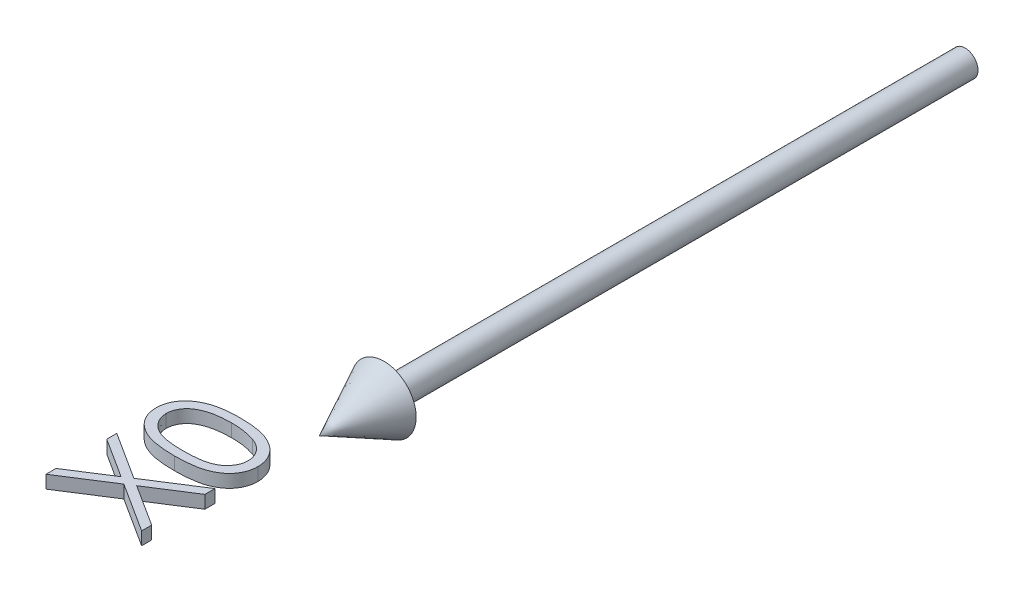
SolidWorks part; units mm, degrees
ref_plane "Front Plane" through (0, 0, 0) normal (0, 0, 1) x (1, 0, 0)
ref_plane "Top Plane" through (0, 0, 0) normal (0, 1, 0) x (1, 0, 0)
ref_plane "Right Plane" through (0, 0, 0) normal (1, 0, 0) x (0, 0, -1)
sketch "Sketch2" plane through (0, 0, 0) normal (0, 1, 0) x (1, 0, 0)
  line L0 (0, 41.95) -> (0, -114.4521) construction
  line L1 (-36.8894, 0) -> (41.4965, 0) construction
  line L2 (0, -100) -> (5, -90)
  line L3 (5, -90) -> (2, -90)
  line L4 (2, -90) -> (2, 0)
  line L5 (2, 0) -> (0, 0)
  line L6 (0, 0) -> (0, -100)
  dimension "D1" = 100
  dimension "D2" = 2
  dimension "D3" = 10
  dimension "D4" = 5
revolve "Revolve1" add sketch "Sketch2" angle 360 about L0
sketch "Sketch3" plane through (0, 0, 0) normal (0, 1, 0) x (1, 0, 0)
  line L0 (0, -103.9528) -> (0, -147.2622) construction
  line L1 (-18.6107, -118.3811) -> (18.3141, -118.3811) construction
  text T0 "X0" font "Century Gothic" height 15
extrude "Boss-Extrude1" add sketch "Sketch3" against normal blind 1 and the other way blind 1 separate body
equation "\"frame_arrow_length\"=100"
equation "\"D1@Sketch2\"=\"frame_arrow_length\""
equation "\"frame_arrow_odA\"=4"
equation "\"D2@Sketch2\"=\"frame_arrow_odA\"/2"
equation "\"frame_arrow_head_od\"=5"
equation "\"D4@Sketch2\"=\"frame_arrow_head_od\""
equation "\"frame_arrow_head_length\"=10"
equation "\"D3@Sketch2\"=\"frame_arrow_head_length\""
equation "\"tvarobot_theta1\"=30"
equation "\"link0_ringA_odA\"= 40"
equation "\"link0_ringA_odB\"= 25"
equation "\"link0_ringA_id\"= 20"
equation "\"link0_ringA_thickness\"= (\"link0_ringA_odB\" - \"link0_ringA_id\")/2"
equation "\"link0_ringA_height\"= 3"
equation "\"link0_ringA_heightA\"= 1.5"
equation "\"link0_ringA_heightB\"=\"link0_ringA_height\"-\"link0_ringA_heightA\""
equation "\"link0_ringB_odA\"= 40"
equation "\"link0_ringB_odB\"= 29"
equation "\"link0_ringB_id\"= \"link0_shaftA_bearing_id\"+1"
equation "\"link0_ringB_thickness\"= (\"link0_ringB_odB\" - \"link0_ringB_id\")/2"
equation "\"link0_ringB_height\"= 3"
equation "\"link0_ringB_heightA\"= 1.5"
equation "\"link0_ringB_heightB\"=\"link0_ringB_height\"-\"link0_ringB_heightA\""
equation "\"link0_shaftA_bearing_od\"=27"
equation "\"link0_shaftA_bearing_id\"=20"
equation "\"link0_shaftA_thrust_bearing_od\"=35"
equation "\"link0_shaftA_thrust_bearing_id\"=20.04"
equation "\"link0_shaftA_retaining_ring_id\"=18.5"
equation "\"link0_shaftA_retaining_ring_groove_width\"=1.5"
equation "\"link0_shaftA_spline_length\"=8.0"
equation "\"link0_shaftA_spline_depth\"=1.0"
equation "\"link0_shaftA_spline_width\"=4.0"
equation "\"link0_shaftA_odA\"=\"link0_shaftA_bearing_id\""
equation "\"link0_shaftA_odB\"=35"
equation "\"link0_shaftA_odC\"=\"link0_shaftA_bearing_id\""
equation "\"link0_shaftA_odD\"=\"link0_shaftA_odC\"-2*\"link0_shaftA_spline_depth\""
equation "\"link0_shaftA_odE\"=\"link0_shaftA_bearing_id\""
equation "\"link0_shaftA_odF\"=\"link0_shaftA_odE\"-2*\"link0_shaftA_spline_depth\""
equation "\"link0_shaftA_idA\"=10"
equation "\"link0_shaftA_idB\"=6"
equation "\"link0_shaftA_length\"=39.5"
equation "\"link0_shaftA_lengthA\"=8.0"
equation "\"link0_shaftA_lengthB\"=12.0"
equation "\"link0_shaftA_lengthC\"=35.0"
equation "\"link0_shaftA_lengthD\"=39.0"
equation "\"link0_shaftA_lengthE\"=\"link0_shaftA_length\"-\"link0_shaftA_lengthD\""
equation "\"link0_shaftA_offsetX\"=11"
equation "\"link0_shaftA_offsetY\"=0"
equation "\"link0_shaftA_bolt_pattern_dia\"=14"
equation "\"link0_motor_center_dist\"=26"
equation "\"link0_46t_pulley_spline_length\"=8"
equation "\"link0_46t_pulley_spline_depth\"=\"link0_shaftA_spline_depth\"*1.025"
equation "\"link0_46t_pulley_spline_width\"=\"link0_shaftA_spline_width\"*1.05"
equation "\"link0_46t_pulley_idA\"=\"link0_shaftA_bearing_id\"*1.025"
equation "\"link0_46t_pulley_idB\"=\"link0_46t_pulley_idA\"-2*\"link0_46t_pulley_spline_depth\""
equation "\"link0_shaftB_spline_length\"=10"
equation "\"link0_shaftB_spline_depth\"=1.0"
equation "\"link0_shaftB_spline_width\"=1.25"
equation "\"link0_shaftB_length\"=7"
equation "\"link0_shaftB_lengthA\"=1.5"
equation "\"link0_shaftB_lengthB\"=2.75"
equation "\"link0_shaftB_odA\"=32"
equation "\"link0_shaftB_odB\"=22"
equation "\"link0_shaftB_odC\"=20"
equation "\"link0_shaftB_idA\"=10"
equation "\"link0_shaftB_bolt_diameter\"=19"
equation "\"link0_shaftB_bearing_od\"=27"
equation "\"link0_shaftB_bearing_id\"=20"
equation "\"link0_motor_length\"=46.5"
equation "\"link0_motor_width\"=28.5"
equation "\"link0_motor_height\"=34"
equation "\"link0_motor_offset\"=8"
equation "\"link0_shellA_thickness\"=2.5"
equation "\"link0_shellB_thickness\"=\"link0_shellA_thickness\""
equation "\"link0_plateA_shellA_height\"=48"
equation "\"link0_shellA_width\" =\"link0_plateA_width\""
equation "\"link0_shellA_height\" = \"link0_plateA_shellA_height\"-\"link0_plateA_height\""
equation "\"link0_shellA_length\" = \"link0_plateA_lengthB\" "
equation "\"link0_shellB_length\"=\"link0_shellA_length\""
equation "\"link0_shellA_radius\" = 0.375*25.4"
equation "\"link0_shellA_radiusA\"= \"link0_plateA_radiusA\""
equation "\"link0_shellA_radiusB\"= \"link0_plateA_radiusB\""
equation "\"link0_shellA_radiusC\"= 3"
equation "\"link0_postA_height\"=7"
equation "\"link0_postA_width\"=16"
equation "\"link0_postA_length\"=20"
equation "\"link0_postA_posX\"=22"
equation "\"link0_postA_posY\"=17.5"
equation "\"link0_postA_pocket_width\"=6.0"
equation "\"link0_postA_pocket_length\"=2.5"
equation "\"link0_postA_pocket_depth\"=9"
equation "\"link0_postA_pocket_posZ\"=10"
equation "\"link0_postB_height\"=7"
equation "\"link0_postB_width\"=16"
equation "\"link0_postB_length\"=20"
equation "\"link0_postB_posX\"=22"
equation "\"link0_postB_posY\"=17.5"
equation "\"link0_postB_id\"=3.0"
equation "\"link0_postB_pocket_width\"=6.0"
equation "\"link0_postB_pocket_length\"=2.5"
equation "\"link0_postB_pocket_depth\"=9"
equation "\"link0_postB_pocket_posZ\"=10"
equation "\"link0_postC_height\"=7"
equation "\"link0_postC_width\"=16"
equation "\"link0_postC_length\"=20"
equation "\"link0_postC_posX\"=22"
equation "\"link0_postC_posY\"=17.5"
equation "\"link0_postC_id\"=3.0"
equation "\"link0_postC_pocket_width\"=6.0"
equation "\"link0_postC_pocket_length\"=2.5"
equation "\"link0_postC_pocket_depth\"=9"
equation "\"link0_postC_pocket_posZ\"=10"
equation "\"link0_postD_height\"=7"
equation "\"link0_postD_width\"=16"
equation "\"link0_postD_length\"=20"
equation "\"link0_postD_posX\"=22"
equation "\"link0_postD_posY\"=17.5"
equation "\"link0_postD_id\"=3.0"
equation "\"link0_postD_pocket_width\"=6.0"
equation "\"link0_postD_pocket_length\"=3.0"
equation "\"link0_postD_pocket_depth\"=9"
equation "\"link0_postD_pocket_posZ\"=10"
equation "\"link0_postE_height\"=5"
equation "\"link0_postE_width\"=16"
equation "\"link0_postE_length\"=\"link0_plateE_lengthA\"-\"link0_lip_height\""
equation "\"link0_postE_posZ\"=22"
equation "\"link0_postE_posX\"=17.5"
equation "\"link0_postE_posY\"=22"
equation "\"link0_postE_id\"=3.0"
equation "\"link0_postE_cbore_id\"=6.5"
equation "\"link0_postE_hole_id\"=3"
equation "\"link0_postF_posZ\"=22"
equation "\"link0_postF_posX\"=17.5"
equation "\"link0_postF_posY\"=\"link0_plateB_lengthA\"+4"
equation "\"link0_postF_id\"=3.0"
equation "\"link0_postF_cbore_id\"=6.5"
equation "\"link0_postF_hole_id\"=3"
equation "\"link0_postG_posZ\"=22"
equation "\"link0_postG_posX\"=17.5"
equation "\"link0_postG_posY\"=\"link0_plateB_lengthA\"+12"
equation "\"link0_postG_id\"=3.0"
equation "\"link0_postG_cbore_id\"=6.5"
equation "\"link0_postG_hole_id\"=3"
equation "\"link0_postHIJ_posY\"=6"
equation "\"link0_postH_posX\"=28"
equation "\"link0_postH_posY\"=20"
equation "\"link0_postH_posZ\"=20"
equation "\"link0_postH_length\"=10"
equation "\"link0_postI_posX\"=28"
equation "\"link0_postI_posY\"=20"
equation "\"link0_postI_posZ\"=135"
equation "\"link0_postI_length\"=10"
equation "\"link0_postJ_posX\"=28"
equation "\"link0_postJ_posY\"=20"
equation "\"link0_postJ_posZ\"=175"
equation "\"link0_postJ_length\"=10"
equation "\"link0_postK_posX\"=28"
equation "\"link0_postK_posY\"=20"
equation "\"link0_postK_posZ\"=175"
equation "\"link0_postK_length\"=10"
equation "\"link0_postL_posX\"=28"
equation "\"link0_postL_posY\"=20"
equation "\"link0_postL_posZ\"=135"
equation "\"link0_postL_length\"=10"
equation "\"link0_postM_posX\"=28"
equation "\"link0_postM_posY\"=20"
equation "\"link0_postM_posZ\"=35"
equation "\"link0_postM_length\"=10"
equation "\"link0_plateA_lengthA\"=30"
equation "\"link0_plateA_lengthB\"=150"
equation "\"link0_plateA_lengthC\"=30"
equation "\"link0_plateA_length\"=\"link0_plateA_lengthA\"+\"link0_plateA_lengthB\"+\"link0_plateA_lengthC\""
equation "\"link0_plateA_width\"=  68"
equation "\"link0_plateA_height\"= \"link0_plateA_radiusA\""
equation "\"link0_plateA_thickness\"=\"link0_shellA_thickness\""
equation "\"link0_plateA_radius\"= 9.5"
equation "\"link0_plateA_radiusA\"= 18"
equation "\"link0_plateA_radiusB\"= 18"
equation "\"link0_plateA_radiusC\"= 3"
equation "\"link0_plateB_length\"= 40"
equation "\"link0_plateB_width\"= \"link0_plateA_width\"*1.005"
equation "\"link0_plateB_height\"= \"link0_plateA_shellA_height\"*1.005"
equation "\"link0_plateB_lengthA\"=\"link0_lip_height\"+\"link0_plateD_thickness\"+\"link0_motor_mount_thickness\""
equation "\"link0_plateB_lengthB\"=\"link0_plateB_height\"-\"link0_plateB_lengthA\""
equation "\"link0_plateB_radiusA\"= \"link0_plateA_radiusA\""
equation "\"link0_plateB_radiusB\"= \"link0_plateA_radiusB\""
equation "\"link0_plateB_radiusC\"= 3"
equation "\"link0_plateB_idA\"=\"link0_shaftA_odC\"+1"
equation "\"link0_plateB_idB\"=\"link0_shaftA_bearing_od\"-2"
equation "\"link0_plateB_idC\"=\"link0_shaftA_bearing_od\"*1.005"
equation "\"link0_plateB_idD\"=\"link0_shaftA_thrust_bearing_od\"+1 "
equation "\"link0_plateB_depthA\"=1.0"
equation "\"link0_plateB_depthB\"=2.0"
equation "\"link0_plateB_depthC\"=8"
equation "\"link0_plateB_depthD\"=\"link0_plateB_length\"-\"link0_lip_height\"-\"link0_plateD_thickness\" "
equation "\"link0_plateC_length\"=\"link0_plateB_length\""
equation "\"link0_plateC_width\"= \"link0_plateB_width\""
equation "\"link0_plateC_height\"= .1*25.4"
equation "\"link0_plateA_hole_od\" = 0.1*25.4"
equation "\"link0_plateA_hole_delx\" = 0.5*25.4"
equation "\"link0_plateA_hole_delz\" = 0.75*25.4"
equation "\"link0_plateA_hole_offx\" = 0.0*25.4"
equation "\"link0_plateA_hole_offz\" = \"link0_plateA_length\"/2"
equation "\"link0_plateB_hole_od\" = 0.1*25.4"
equation "\"link0_plateB_hole_delx\"= 0.75*25.4"
equation "\"link0_plateB_hole_delz\"= 0.75*25.4"
equation "\"link0_plateB_hole_offx\"= 0.0*25.4"
equation "\"link0_plateB_hole_offz\"= 0.0*25.4"
equation "\"link0_plateC_hole_od\"= 0.1*25.4"
equation "\"link0_plateC_hole_delx\"= 0.75*25.4"
equation "\"link0_plateC_hole_delz\"= 0.75*25.4"
equation "\"link0_plateC_hole_offx\"= 0.0*25.4"
equation "\"link0_plateC_hole_offz\"= 0.0*25.4"
equation "\"link0_plateD_height\"=\"link0_plateB_height\"-2*\"link0_shellA_thickness\""
equation "\"link0_plateD_width\"=\"link0_plateB_width\"-2*\"link0_shellA_thickness\""
equation "\"link0_plateD_thickness\"=10"
equation "\"link0_plateD_radiusA\"=\"link0_plateB_radiusA\"-\"link0_shellA_thickness\""
equation "\"link0_plateD_odA\"= .375*25.4"
equation "\"link0_plateD_odB\"= .375*25.4"
equation "\"link0_plateD_bearing_id\"=20"
equation "\"link0_plateD_bearing_od\"=27"
equation "\"link0_plateE_radiusA\"=\"link0_plateA_radiusA\""
equation "\"link0_plateE_radiusB\"=\"link0_plateA_radiusB\""
equation "\"link0_plateE_radiusC\"=8.0"
equation "\"link0_plateE_length\"=30"
equation "\"link0_plateE_lengthA\"=16"
equation "\"link0_plateE_height\"=\"link0_plateB_height\""
equation "\"link0_plateE_width\"=\"link0_plateB_width\""
equation "\"link0_plateE_odA\"=\"gantry_coupler_id\"*0.99"
equation "\"link0_plateE_idA\"=\"link0_plateE_odA\"-20.0"
equation "\"link0_plateE_spline_depth\"=\"link0_poleA_spline_depth\"*1.05"
equation "\"link0_plateE_spline_width\"=\"link0_poleA_spline_width\"*1.075"
equation "\"link0_plateE_spline_length\"=\"link0_poleA_spline_length\""
equation "\"link0_plateE_coupler_length\"=46"
equation "\"link0_lip_height\"=5.0"
equation "\"link0_lip_thickness\"=2.0"
equation "\"link0_motor_mount_thickness\"=8.0"
equation "\"link0_motor_mount_idA\"=22"
equation "\"link0_motor_mount_idB\"=\"link0_shaftB_bearing_od\"*1.005"
equation "\"link0_motor_mount_idC\"=\"link0_shaftB_bearing_od\"-2"
equation "\"link0_motor_mount_depthA\"=5.5"
equation "\"link0_motor_mount_height\"=\"link0_plateD_height\""
equation "\"link0_motor_mount_width\"=\"link0_plateD_width\""
equation "\"link0_motor_mountL_height\"=36"
equation "\"link0_motor_mountL_heightA\"=12"
equation "\"link0_motor_mountL_length\"=50"
equation "\"link0_motor_mountL_lengthA\"=36"
equation "\"gantry_coupler_od\"=25.4*2.0"
equation "\"gantry_coupler_id\"=1.645*25.4"
equation "\"gantry_coupler_offsetX\"=\"link0_plateE_width\"/2"
equation "\"link0_poleA_odA\"=20"
equation "\"link0_poleA_odB\"=36"
equation "\"link0_poleA_idA\"=\"link0_poleA_odA\"-2*\"link0_poleA_thickness\""
equation "\"link0_poleA_idB\"=(\"link0_plateE_idA\"/2+1.5*\"link0_lip_thickness\")*1.04"
equation "\"link0_poleA_thickness\"=3.5"
equation "\"link0_poleA_length\"=100"
equation "\"link0_poleA_lengthA\"=18.5"
equation "\"link0_poleA_lengthB\"=80"
equation "\"link0_poleA_gasket_thickness\"=1.5"
equation "\"link0_poleA_spline_depth\"=1.0"
equation "\"link0_poleA_spline_width\"=4.0"
equation "\"link0_poleA_spline_length\"=10.0"
equation "\"link1_plateB_length\"=30"
equation "\"link1_lip_height\"=\"link0_lip_height\""
equation "\"link0_tension_plateA_width\"=12"
equation "\"link0_tension_plateA_lengthA\"=10.5"
equation "\"link0_tension_plateB_width\"=\"link0_tension_plateA_width\""
equation "\"link0_tension_plateB_lengthA\"=\"link0_tension_plateA_lengthA\""
equation "\"link0_tension_wheelA_posZ\"=7"
equation "\"link0_tension_wheelA_posX\"=\"link0_plateD_height\"/2-\"link0_tension_plateA_lengthA\""
equation "\"link0_m2_clear_hole_id\"=2.35"
equation "\"link0_m2_insert_hole_id\"=2.5"
equation "\"link0_m2_tap_hole_id\"=1.75"
equation "\"link0_m2_nut_socket_width\"=4.25"
equation "\"link0_m2_nut_socket_depth\"=2.5"
equation "\"link0_m2_cbore_id\"=3.75"
equation "\"link0_m2_cbore_depth\"=7"
equation "\"link0_m2_5_clear_hole_id\"=2.75"
equation "\"link0_m2_5_insert_hole_id\"=2.75"
equation "\"link0_m2_5_tap_hole_id\"=2.25"
equation "\"link0_m2_5_nut_socket_width\"=5.25"
equation "\"link0_m2_5_nut_socket_depth\"=2.5"
equation "\"link0_m2_5_cbore_id\"=4.75"
equation "\"link0_m2_5_cbore_depth\"=2.5"
equation "\"link0_m2_5_insert_access_length\"=6.0"
equation "\"link0_m2_5_insert_access_width\"=3.0"
equation "\"link0_m3_clear_hole_id\"=3.25"
equation "\"link0_m3_insert_hole_id\"=3"
equation "\"link0_m3_tap_hole_id\"=2.75"
equation "\"link0_m3_nut_socket_width\"=5.75"
equation "\"link0_m3_nut_socket_depth\"=4.0"
equation "\"link0_m3_cbore_id\"=5.75"
equation "\"link0_m3_cbore_depth\"=3.5"
equation "\"link0_m3_insert_access_length\"=4.5"
equation "\"link0_m3_insert_access_width\"=3.5"
equation "\"link0_rpi_mount_height\"=6"
equation "\"link0_rpi_mount_width\"=49"
equation "\"link0_rpi_mount_length\"=58"
equation "\"link0_rpi_mount_post_od\"=6"
equation "\"link0_rpi_mount_posZ\"=72"
equation "\"link0_rpi_mount_posX\"=11.5"
equation "\"link0_mcu_mount_height\"=5"
equation "\"link0_mcu_mount_width\"=49"
equation "\"link0_mcu_mount_length\"=58"
equation "\"link0_mcu_mount_post_od\"=6"
equation "\"link0_mcu_mount_posZ\"=164"
equation "\"link0_mcu_mount_posX\"=4"
equation "\"link0_pwr_mount_height\"=4"
equation "\"link0_pwr_mount_width\"=15.75"
equation "\"link0_pwr_mount_length\"=75.75"
equation "\"link0_pwr_mount_post_od\"=6"
equation "\"link0_pwr_mount_posZ\"=75"
equation "\"link0_pwr_mount_posX\"=16"
equation "\"link0_pwr_board_height\"=6"
equation "\"link0_pwr_board_width\"=21"
equation "\"link0_pwr_board_length\"=80"
